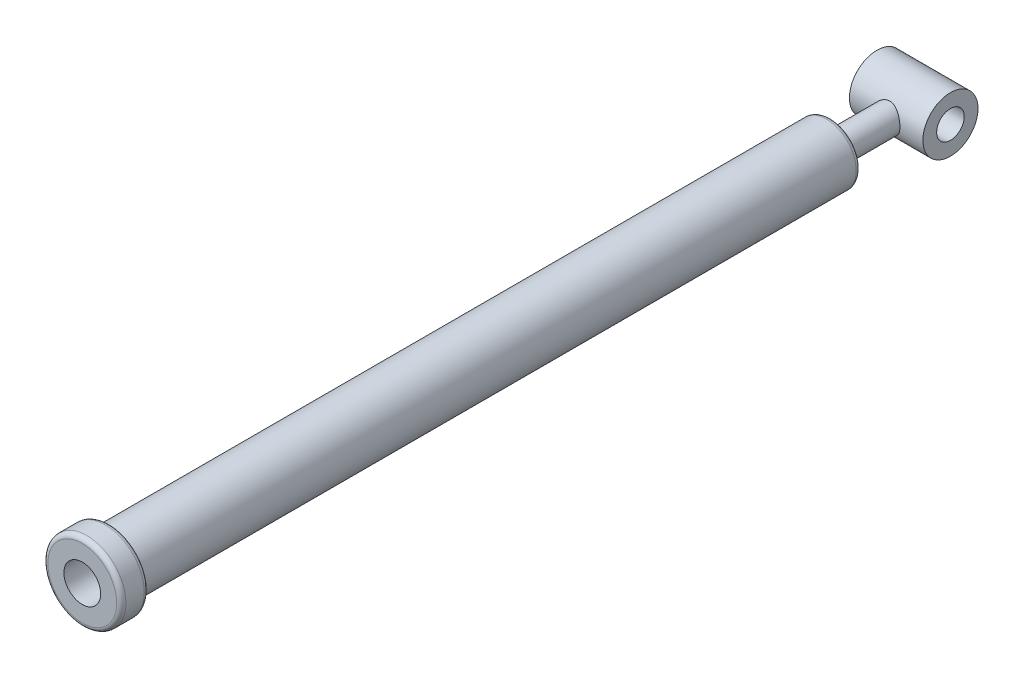
SolidWorks part; units mm, degrees
ref_plane "Front Plane" through (0, 0, 0) normal (0, 0, 1) x (1, 0, 0)
ref_plane "Top Plane" through (0, 0, 0) normal (0, 1, 0) x (1, 0, 0)
ref_plane "Right Plane" through (0, 0, 0) normal (1, 0, 0) x (0, 0, -1)
sketch "Sketch1" plane through (0, 0, 0) normal (0, 0, 1) x (1, 0, 0)
  circle A0 centre (0, 0) radius 42.5
  circle A1 centre (0, 0) radius 20
  dimension "D1" = 85
  dimension "D2" = 40
extrude "Boss-Extrude1" add sketch "Sketch1" against normal blind 30
sketch "Sketch2" plane through (0, 0, -30) normal (0, 0, -1) x (-1, 0, 0)
  circle A0 centre (0, 0) radius 32.5
  circle A1 centre (0, 0) radius 20 construction
  circle A2 centre (0, 0) radius 20
  dimension "D1" = 65
extrude "Boss-Extrude2" add sketch "Sketch2" along normal blind 780
sketch "Sketch3" plane through (0, 0, -810) normal (0, 0, -1) x (-1, 0, 0)
  circle A1 centre (0, 0) radius 32.5
  circle A2 centre (0, 0) radius 32.5
  dimension "D1" = 0
extrude "Boss-Extrude3" add sketch "Sketch3" along normal blind 5
sketch "Sketch4" plane through (0, 0, -815) normal (0, 0, -1) x (-1, 0, 0)
  circle A0 centre (0, 0) radius 15
  dimension "D1" = 30
extrude "Boss-Extrude4" add sketch "Sketch4" along normal blind 65
sketch "Sketch5" plane through (0, 0, 0) normal (1, 0, 0) x (0, 0, -1)
  line L0 (815, -15) -> (815, 15) construction
  line L1 (905, 0) -> (880, 0) construction
  line L2 (880, -15) -> (880, 15) construction
  circle A0 centre (905, 0) radius 30
  circle A1 centre (905, 0) radius 15
  dimension "D2" = 30
  dimension "D3" = 60
  dimension "D1" = 90
extrude "Boss-Extrude5" add sketch "Sketch5" along normal mid plane 80
fillet "Fillet1" radius 5 3 edges at (42.5, 0, 0) (42.5, 0, -30) (-32.5, 0, -815)
